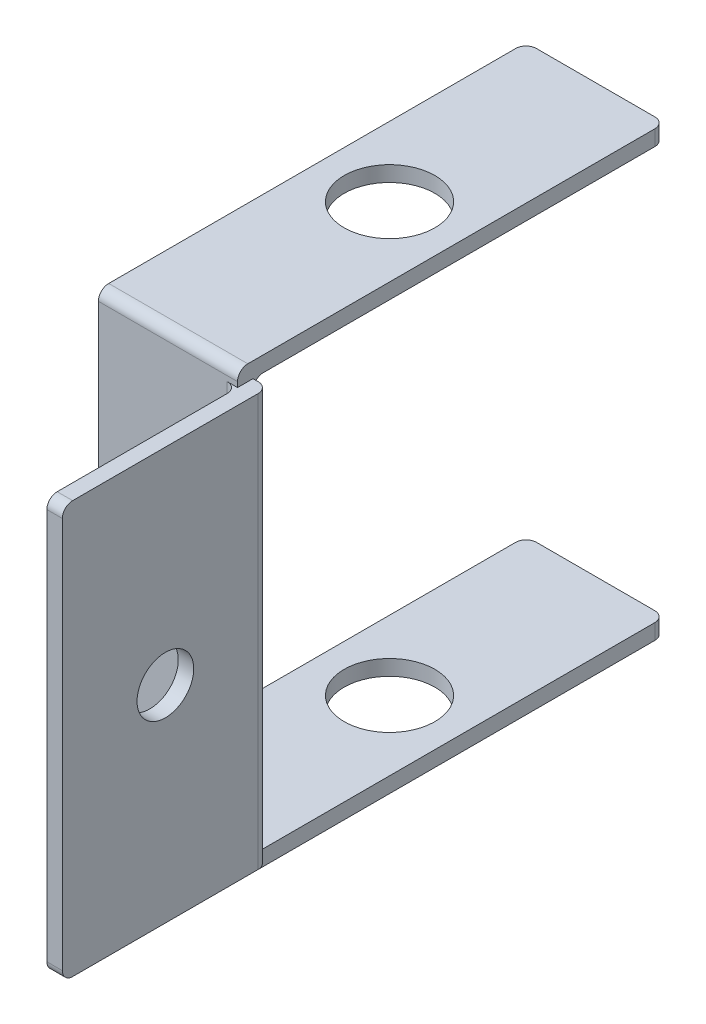
SolidWorks part; units mm, degrees
ref_plane "前视基准面" through (0, 0, 0) normal (0, 0, 1) x (1, 0, 0)
ref_plane "上视基准面" through (0, 0, 0) normal (0, 1, 0) x (1, 0, 0)
ref_plane "右视基准面" through (0, 0, 0) normal (1, 0, 0) x (0, 0, -1)
other "Configuration Table"
sketch "草图1" plane through (0, 0, 0) normal (0, 0, 1) x (1, 0, 0)
  line L0 (0, 0) -> (15, 0)
  line L1 (15, 0) -> (15, -40)
  line L2 (15, -40) -> (0, -40)
  line L3 (0, -40) -> (0, 0)
  line L4 (15, -40) -> (13.5, -40)
  line L5 (13.5, -40) -> (13.5, 0)
  dimension "D1" = 13.5
  dimension "D2" = 1.5
  dimension "D3" = 40
extrude "凸台-拉伸1" add sketch "草图1" along normal blind 1.5 contours L2 L5 L0 L3 region at (6.75, -20, 0)
extrude "凸台-拉伸2" add sketch "草图1<3>" along normal blind 20 contours L5 L2 L1 L0 region at (14.25, -20, 0)
sketch "草图1<3>" plane through (0, 0, 0) normal (0, 0, 1) x (1, 0, 0) same geometry as "草图1"
sketch "草图2" plane through (0, 0, 1.5) normal (0, 0, 1) x (1, 0, 0)
  line L0 (0, 0) -> (0, 1.5)
  line L1 (0, 1.5) -> (13.5, 1.5)
  line L2 (13.5, 1.5) -> (13.5, 0)
  line L3 (13.5, 0) -> (0, 0)
  line L4 (0, -40) -> (0, -41.5)
  line L5 (0, -41.5) -> (13.5, -41.5)
  line L6 (13.5, -41.5) -> (13.5, -40)
  line L7 (13.5, -40) -> (0, -40)
extrude "凸台-拉伸3" add sketch "草图2" against normal blind 41.5
sketch "草图3" plane through (13.5, 0, 0) normal (-1, 0, 0) x (0, 0, 1)
  line L0 (0, -40) -> (0, 0) construction
  line L2 (20, -40) -> (1.5, -40) construction
  circle A0 centre (10, -20) radius 2.75
  dimension "D1" = 10
  dimension "D2" = 20
  dimension "D3" = 5.5
extrude "切除-拉伸1" cut sketch "草图3" against normal blind 2
sketch "草图5" plane through (0, -41.5, 0) normal (0, -1, 0) x (1, 0, 0)
  line L0 (6.75, -40) -> (6.75, -20)
  line L1 (0, -40) -> (13.5, -40) construction
  circle A0 centre (6.75, -20) radius 4.4
  dimension "D1" = 8.8
fillet "圆角1" radius 1 12 edges at (14.25, 0, 20) (14.25, -40, 20) (13.5, -20, 1.5) (6.75, 0, 0) (6.75, 1.5, 1.5) (6.75, -40, 0) (15, -20, 0) (6.75, -41.5, 1.5) (13.5, 0.75, -40) (13.5, -40.75, -40) (0, -40.75, -40) (0, 0.75, -40)
sketch "草图10" plane through (0, 0, 1.5) normal (0, 0, 1) x (1, 0, 0)
  line L0 (0, -20) -> (6.25, -20)
  line L1 (0, -40.5) -> (0, 0.5) construction
  circle A0 centre (6.25, -20) radius 4.4
  dimension "D1" = 8.8
extrude "切除-拉伸2" cut sketch "草图10" against normal blind 10 contours A0 region at (6.25, -24.2755, 1.5)
extrude "切除-拉伸3" cut sketch "草图5" against normal blind 60 contours A0 region at (9.7733, -41.5, -23.0233)
